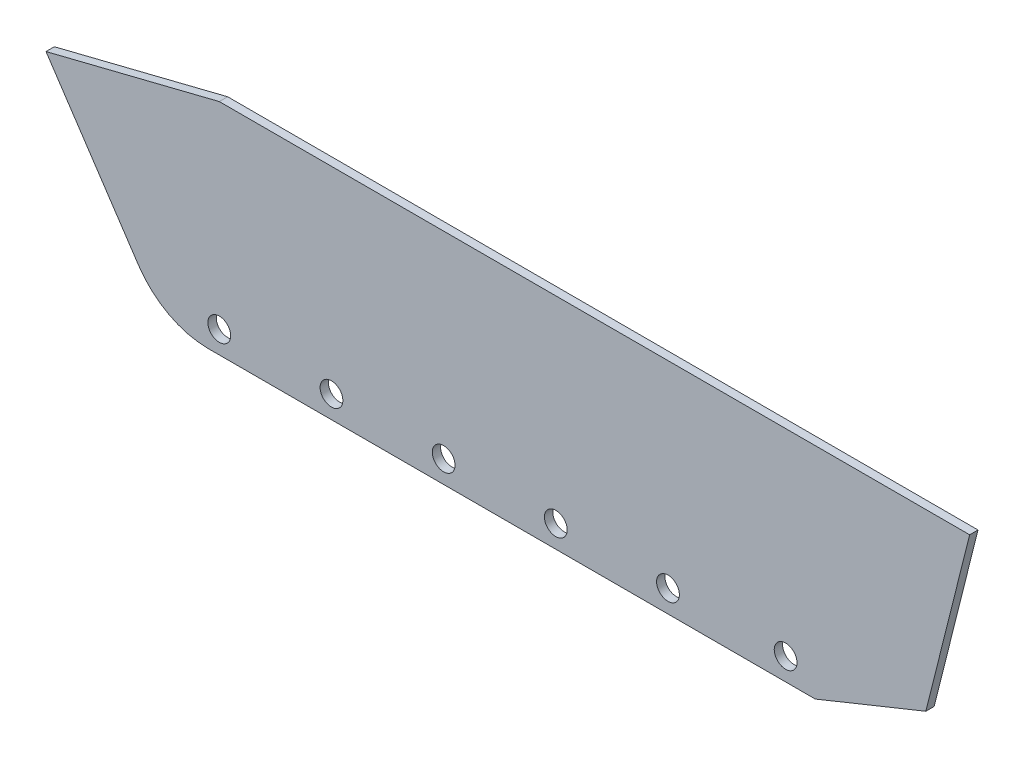
SolidWorks part; units mm, degrees
material "5052-H34"
ref_plane "Front Plane" through (0, 0, 0) normal (0, 0, 1) x (1, 0, 0)
ref_plane "Top Plane" through (0, 0, 0) normal (0, 1, 0) x (1, 0, 0)
ref_plane "Right Plane" through (0, 0, 0) normal (1, 0, 0) x (0, 0, -1)
sketch "Sketch1" plane through (0, 0, 0) normal (0, 0, 1) x (1, 0, 0)
  line L1 (428.1206, 33.3333) -> (428.1206, 28.5708)
  line L3 (428.1206, 28.5708) -> (0, 28.5708)
  line L4 (0, 28.5708) -> (-98.8794, 3.851)
  line L6 (-98.8794, 3.851) -> (-31.8794, -96.649)
  line L7 (428.1206, 28.5708) -> (403.1206, -71.149)
  line L9 (403.1206, -71.149) -> (366, -96.649)
  line L10 (-31.8794, -96.649) -> (366, -96.649)
  circle A0 centre (0, -83.899) radius 6.5
  circle A1 centre (64, -83.899) radius 6.5
  circle A2 centre (128, -83.899) radius 6.5
  circle A3 centre (192, -83.899) radius 6.5
  circle A4 centre (256, -83.899) radius 6.5
  circle A5 centre (323.1206, -83.899) radius 6.5
  point P0 (-48.8794, -71.149)
  point P2 (-31.8794, -96.649)
  point P8 (48, -83.899)
  point P9 (403.1206, -71.149)
  dimension "D2" = 48
  dimension "D4" = 64
  dimension "D1" = 25.5
  dimension "D3" = 75
  dimension "D5" = 25
  dimension "D6" = 80
  dimension "D7" = 527
  dimension "D9" = 64
  dimension "D10" = 64
  dimension "D11" = 64
  dimension "D12" = 123.69
  dimension "D13" = 12.75
extrude "Boss-Extrude1" add sketch "Sketch1" along normal blind 4.7625 contours L3 L4 L6 L10 L9 L7
extrude "Cut-Extrude1" cut sketch "Sketch1<4>" along normal through all contours A0 | A1 | A2 | A3 | A4 | A5 region at (0, -83.899, 0)
sketch "Sketch1<4>" plane through (0, 0, 0) normal (0, 0, 1) x (1, 0, 0) same geometry as "Sketch1"
sketch "Sketch2" plane through (0, 0, 0) normal (0, 0, -1) x (-1, 0, 0)
  circle A0 centre (-291.1206, -83.899) radius 6.5
  circle A2 centre (-241.5603, -124.3932) radius 6.5
  circle A3 centre (-192, -83.899) radius 6.5
  circle A4 centre (-128, -83.899) radius 6.5
  circle A5 centre (-64, -83.899) radius 6.5
  circle A6 centre (0, -83.899) radius 6.5
  dimension "D2" = 0
  dimension "D3" = 64
  dimension "D4" = 64
  dimension "D5" = 64
  dimension "D6" = 64
  dimension "D7" = 64
  dimension "D1" = 32
sketch "Sketch5" plane through (0, 0, 0) normal (0, 0, -1) x (-1, 0, 0)
  line L0 (48.8794, -71.149) -> (-14.2353, -96.649)
  line L1 (31.8794, -96.649) -> (-366, -96.649) construction
  line L2 (-14.2353, -96.649) -> (31.8794, -96.649)
  line L3 (31.8794, -96.649) -> (48.8794, -71.149)
  line L6 (-366, -96.649) -> (-403.1206, -71.149)
  line L7 (-403.1206, -71.149) -> (-352, -71.149)
  line L9 (-352, -71.149) -> (-326.5, -96.649)
  line L11 (-366, -96.649) -> (-326.5, -96.649)
  dimension "D1" = 22
  dimension "D2" = 45
extrude "Cut-Extrude2" [suppressed] cut sketch "Sketch5" against normal up to next
sketch "Sketch6" plane through (0, 0, 4.7625) normal (0, 0, 1) x (1, 0, 0)
  line L0 (-48.8794, -71.149) -> (14.2353, -96.649)
  line L1 (-31.8794, -96.649) -> (366, -96.649) construction
  line L2 (14.2353, -96.649) -> (-31.8794, -96.649)
  line L3 (-31.8794, -96.649) -> (-48.8794, -71.149)
  dimension "D1" = 158
fillet "Fillet4" radius 48 1 edges at (-31.8794, -96.649, 2.3813)
sketch "Sketch7" plane through (0, 0, 4.7625) normal (0, 0, 1) x (1, 0, 0)
  line L0 (403.1206, -71.149) -> (340.0059, -96.649)
  line L1 (-31.8794, -96.649) -> (366, -96.649) construction
  line L2 (340.0059, -96.649) -> (366, -96.649)
  line L3 (366, -96.649) -> (403.1206, -71.149)
  dimension "D1" = 22
extrude "Cut-Extrude3" cut sketch "Sketch7" against normal blind 10
